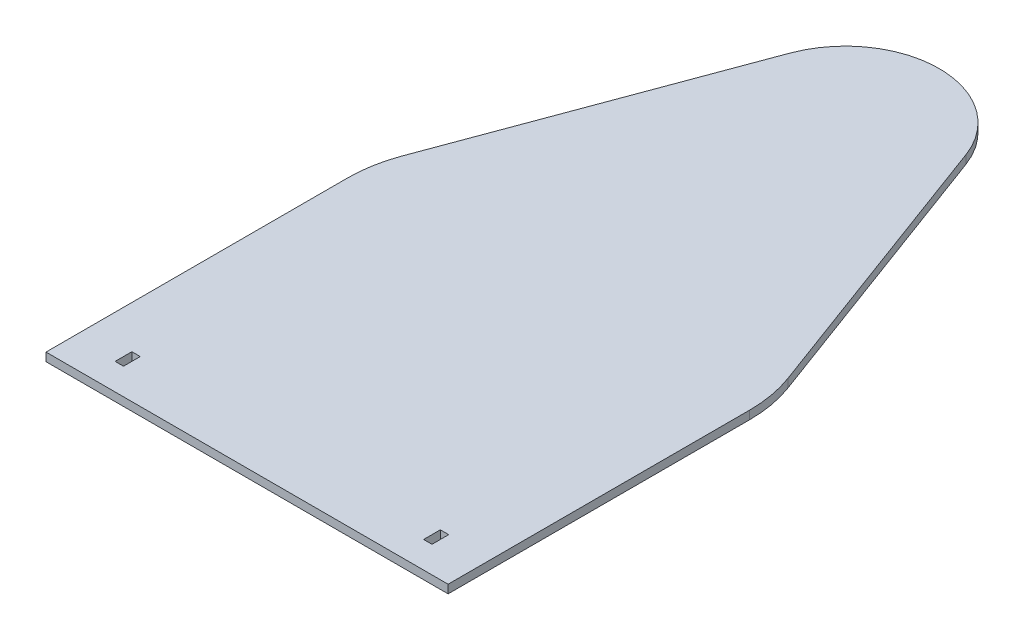
SolidWorks part; units mm, degrees
ref_plane "Front Plane" through (0, 0, 0) normal (0, 0, 1) x (1, 0, 0)
ref_plane "Top Plane" through (0, 0, 0) normal (0, 1, 0) x (1, 0, 0)
ref_plane "Right Plane" through (0, 0, 0) normal (1, 0, 0) x (0, 0, -1)
sketch "Sketch3" plane through (0, 0, 0) normal (0, 1, 0) x (1, 0, 0)
  line L0 (0, 0) -> (0, 114.3)
  line L1 (3.1613, 131.9407) -> (42.8529, 239.1278)
  line L2 (109.5471, 239.1278) -> (149.2387, 131.9407)
  line L3 (152.4, 114.3) -> (152.4, 0)
  line L4 (152.4, 0) -> (0, 0)
  line L5 (76.2, 262.3393) -> (76.2, 0) construction
  line L6 (16.155, 16.3877) -> (19.33, 16.3877)
  line L7 (16.155, 16.3877) -> (16.155, 10.0377)
  line L8 (16.155, 10.0377) -> (19.33, 10.0377)
  line L9 (19.33, 16.3877) -> (19.33, 10.0377)
  line L10 (136.245, 10.0377) -> (133.07, 10.0377)
  line L11 (133.07, 16.3877) -> (133.07, 10.0377)
  line L12 (136.245, 16.3877) -> (133.07, 16.3877)
  line L13 (136.245, 16.3877) -> (136.245, 10.0377)
  arc A0 (42.8529, 239.1278) -> (109.5471, 239.1278) centre (76.2, 226.7793) cw
  arc A1 (0, 114.3) -> (3.1613, 131.9407) centre (50.8, 114.3) cw
  arc A2 (149.2387, 131.9407) -> (152.4, 114.3) centre (101.6, 114.3) cw
  dimension "D1" = 35.56
  dimension "D2" = 50.8
  dimension "D3" = 50.8
  dimension "D4" = 114.3
  dimension "D5" = 152.4
  dimension "D6" = 3.175
  dimension "D7" = 6.35
extrude "Boss-Extrude1" add sketch "Sketch3" along normal blind 3.175
